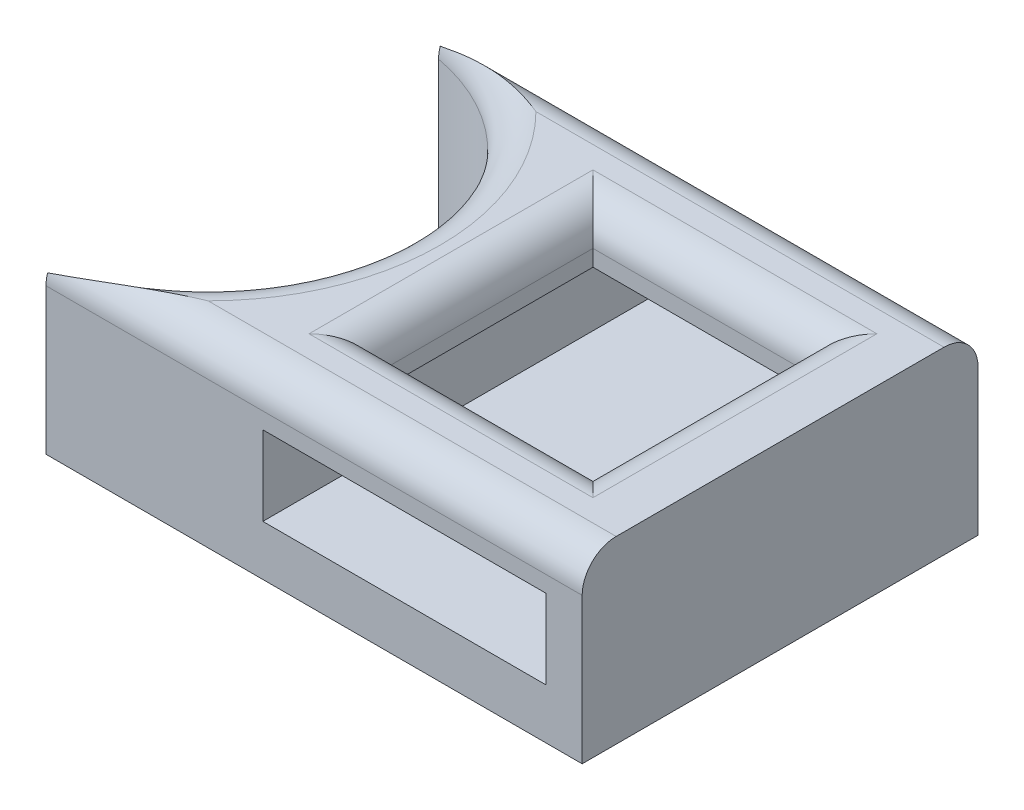
SolidWorks part; units mm, degrees
ref_plane "Front Plane" through (0, 0, 0) normal (0, 0, 1) x (1, 0, 0)
ref_plane "Top Plane" through (0, 0, 0) normal (0, 1, 0) x (1, 0, 0)
ref_plane "Right Plane" through (0, 0, 0) normal (1, 0, 0) x (0, 0, -1)
sketch "Sketch1" plane through (0, 0, 0) normal (0, 1, 0) x (1, 0, 0)
  line L1 (-52.9117, 34.1909) -> (-2.4317, 34.1909)
  line L3 (-52.9117, -0.7341) -> (-2.4317, -0.7341)
  line L4 (-2.4317, 34.1909) -> (-2.4317, -0.7341)
  arc A0 (-52.9117, 34.1909) -> (-52.9117, -0.7341) centre (-52.9117, 16.7284) cw
  dimension "D1" = 50.48
  dimension "D2" = 34.925
extrude "Boss-Extrude1" add sketch "Sketch1" along normal blind 15.875
sketch "Sketch2" plane through (0, 0, 0) normal (0, -1, 0) x (-1, 0, 0)
  line L1 (31.0067, 27.8409) -> (5.6067, 27.8409)
  line L2 (31.0067, 27.8409) -> (31.0067, 24.6659)
  line L3 (31.0067, 24.6659) -> (5.6067, 24.6659)
  line L4 (5.6067, 27.8409) -> (5.6067, 24.6659)
  dimension "D1" = 3.175
  dimension "D2" = 25.4
  dimension "D3" = 3.175
  dimension "D4" = 6.35
sketch "Sketch3" plane through (0, 0, 0) normal (0, -1, 0) x (-1, 0, 0)
  line L0 (2.4317, -0.7341) -> (2.4317, 34.1909) construction
  line L1 (31.0067, 8.7909) -> (5.6067, 8.7909)
  line L2 (31.0067, 8.7909) -> (31.0067, 5.6159)
  line L3 (31.0067, 5.6159) -> (5.6067, 5.6159)
  line L4 (5.6067, 8.7909) -> (5.6067, 5.6159)
  dimension "D1" = 3.175
  dimension "D2" = 3.175
  dimension "D3" = 6.35
  dimension "D4" = 25.4
sketch "Sketch4" plane through (0, 0, -34.1909) normal (0, 0, -1) x (-1, 0, 0)
  line L0 (49.7367, 15.875) -> (49.7367, 0) construction
  line L1 (2.4317, 15.875) -> (52.9117, 15.875) construction
  line L2 (2.4317, 0) -> (52.9117, 0) construction
  dimension "D1" = 3.175
sketch "Sketch5" plane through (0, 0, -34.1909) normal (0, 0, -1) x (-1, 0, 0)
  line L1 (49.7367, 15.875) -> (52.9117, 15.875)
  line L2 (49.7367, 15.875) -> (49.7367, 0)
  line L3 (49.7367, 0) -> (52.9117, 0)
  line L4 (52.9117, 15.875) -> (52.9117, 0)
extrude "Cut-Extrude1" cut sketch "Sketch5" against normal blind 3.175
sketch "Sketch6" plane through (0, 0, 0.7341) normal (0, 0, 1) x (1, 0, 0)
  line L0 (-49.7367, 15.875) -> (-49.7367, 0) construction
  line L1 (-52.9117, 15.875) -> (-2.4317, 15.875) construction
  line L2 (-52.9117, 0) -> (-2.4317, 0) construction
  line L4 (-52.9117, 15.875) -> (-49.7367, 15.875)
  line L5 (-52.9117, 15.875) -> (-52.9117, 0)
  line L6 (-52.9117, 0) -> (-49.7367, 0)
  line L7 (-49.7367, 15.875) -> (-49.7367, 0)
  dimension "D1" = 3.175
extrude "Cut-Extrude2" cut sketch "Sketch6" against normal blind 3.175
sketch "Sketch7" plane through (0, 15.875, 0) normal (0, 1, 0) x (1, 0, 0)
  line L0 (-35.4492, 16.7284) -> (-2.4317, 16.7284) construction
  line L1 (-2.4317, -0.7341) -> (-2.4317, 34.1909) construction
  line L3 (-28.4654, 7.2034) -> (-9.4154, 7.2034)
  line L4 (-28.4654, 7.2034) -> (-28.4654, 26.2534)
  line L5 (-28.4654, 26.2534) -> (-9.4154, 26.2534)
  line L6 (-9.4154, 7.2034) -> (-9.4154, 26.2534)
  line L7 (-28.4654, 7.2034) -> (-9.4154, 26.2534) construction
  line L8 (-28.4654, 26.2534) -> (-9.4154, 7.2034) construction
  arc A0 (-49.7367, -0.443) -> (-49.7367, 33.8999) centre (-52.9117, 16.7284) ccw construction
  point P7 (-18.9404, 16.7284)
  dimension "D1" = 19.05
  dimension "D2" = 19.05
extrude "Cut-Extrude4" cut sketch "Sketch7" against normal blind 10
sketch "Sketch8" plane through (0, 0, -34.1909) normal (0, 0, -1) x (-1, 0, 0)
  line L0 (2.4317, 7.9375) -> (49.6722, 7.9375) construction
  line L1 (2.4317, 15.875) -> (2.4317, 0) construction
  line L3 (30.6067, 4.4375) -> (5.6067, 4.4375)
  line L4 (30.6067, 4.4375) -> (30.6067, 11.4375)
  line L5 (30.6067, 11.4375) -> (5.6067, 11.4375)
  line L6 (5.6067, 4.4375) -> (5.6067, 11.4375)
  line L7 (30.6067, 4.4375) -> (5.6067, 11.4375) construction
  line L8 (30.6067, 11.4375) -> (5.6067, 4.4375) construction
  point P4 (18.1067, 7.9375)
  dimension "D1" = 25
  dimension "D2" = 7
  dimension "D3" = 3.175
extrude "Cut-Extrude5" cut sketch "Sketch8" against normal through all
fillet "Fillet3" radius 3 3 edges at (-26.0842, 15.875, -34.1909) (-26.0842, 15.875, 0.7341) (-35.4492, 15.875, -16.7284)
extrude "Cut-Extrude6" cut sketch "Sketch2" against normal blind 4.175
extrude "Cut-Extrude7" cut sketch "Sketch3" against normal blind 4.175
fillet "Fillet4" radius 3 4 edges at (-18.9404, 15.875, -26.2534) (-9.4154, 15.875, -16.7284) (-18.9404, 15.875, -7.2034) (-28.4654, 15.875, -16.7284)
